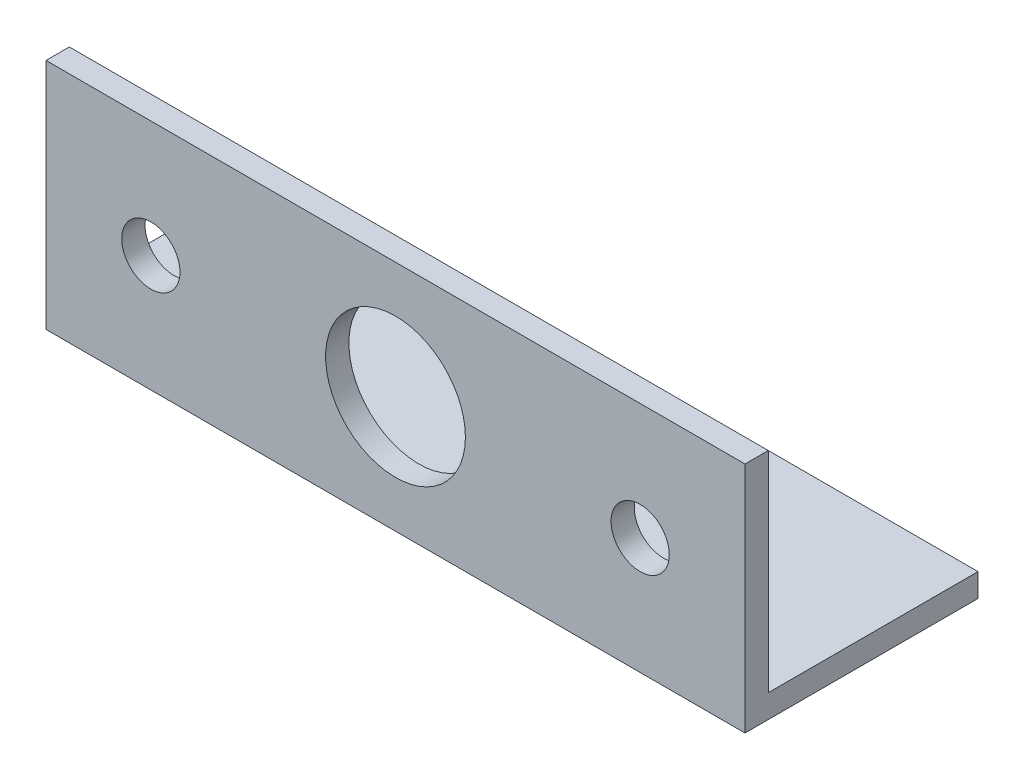
SolidWorks part; units mm, degrees
ref_plane "Front Plane" through (0, 0, 0) normal (0, 0, 1) x (1, 0, 0)
ref_plane "Top Plane" through (0, 0, 0) normal (0, 1, 0) x (1, 0, 0)
ref_plane "Right Plane" through (0, 0, 0) normal (1, 0, 0) x (0, 0, -1)
sketch "Sketch1" plane through (0, 0, 0) normal (1, 0, 0) x (0, 0, -1)
  line L0 (0, 20) -> (0, 0)
  line L1 (0, 0) -> (20, 0)
  line L2 (20, 0) -> (20, 2)
  line L3 (20, 2) -> (2, 2)
  line L4 (2, 2) -> (2, 20)
  line L5 (0, 20) -> (2, 20)
  dimension "D1" = 20
  dimension "D2" = 20
  dimension "D3" = 2
  dimension "D4" = 2
extrude "Boss-Extrude1" add sketch "Sketch1" along normal blind 30 and the other way blind 30
sketch "Sketch2" plane through (0, 0, 0) normal (0, 0, 1) x (1, 0, 0)
  line L0 (-30, 10) -> (30, 10) construction
  line L1 (-30, 20) -> (-30, 0) construction
  line L2 (30, 20) -> (30, 0) construction
  circle A0 centre (-21, 10) radius 2.5
  circle A1 centre (21, 10) radius 2.5
  circle A2 centre (0, 10) radius 6
  dimension "D3" = 5
  dimension "D4" = 5
  dimension "D5" = 12
  dimension "D1" = 42
  dimension "D2" = 9
extrude "Cut-Extrude1" cut sketch "Sketch2" against normal blind 2
